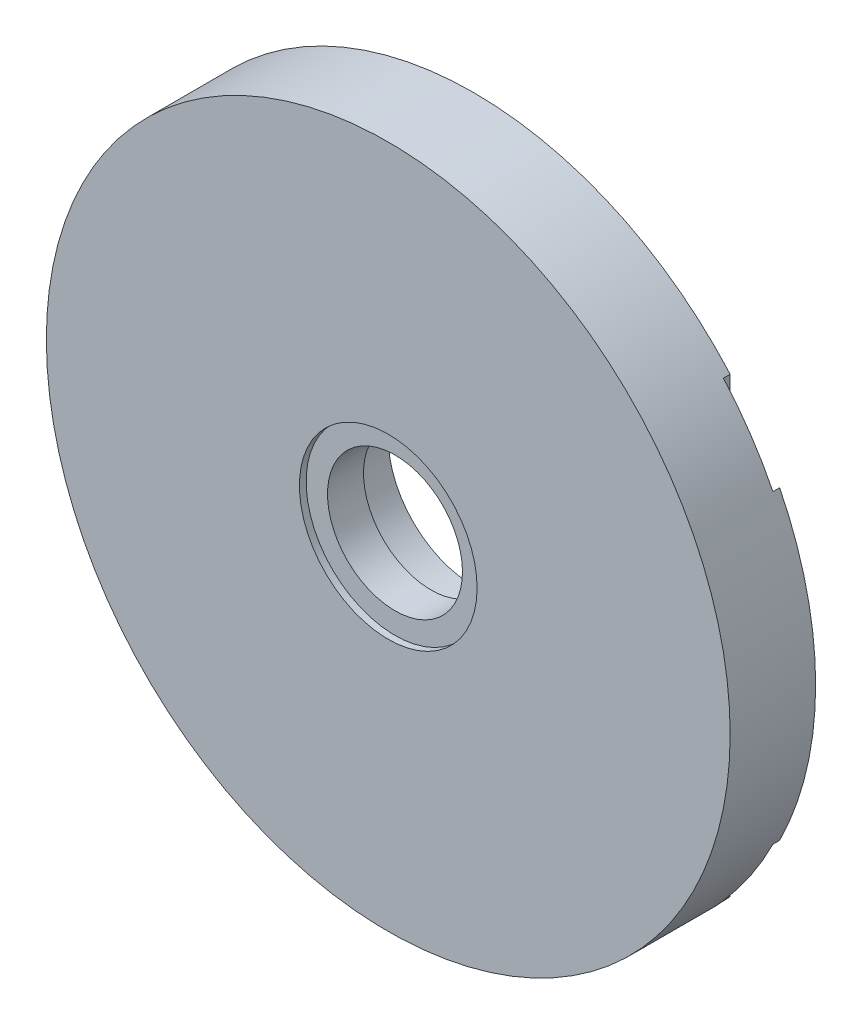
SolidWorks part; units mm, degrees
material "Plain Carbon Steel"
ref_plane "Front Plane" through (0, 0, 0) normal (1, 0, 0) x (0, 1, 0)
ref_plane "Top Plane" through (0, 0, 0) normal (0, 0, 1) x (0, 1, 0)
ref_plane "Right Plane" through (0, 0, 0) normal (0, 1, 0) x (-1, 0, 0)
sketch "Sketch1" plane through (0, 0, 0) normal (0, 0, 1) x (0, 1, 0)
  circle A0 centre (0, 0) radius 50.8
  circle A3 centre (0, 0) radius 10.025
  circle A4 centre (0, 0) radius 13.2
  circle A5 centre (0, 0) radius 12.7
  dimension "D1" = 101.6
  dimension "D2" = 20.05
  dimension "D3" = 26.4
  dimension "D4" = 25.4
extrude "Boss-Extrude1" add sketch "Sketch1" along normal blind 12.7 contours A0 A4 | A4 A3 | A5 A3 region at (0, -49.3632, 0) region at (0, -12.8266, 0) region at (0, -12.3408, 0)
extrude "Cut-Extrude1" cut sketch "Sketch1<3>" against normal blind 1 from surface contours A5 A3 | A4 A5 region at (0, -12.8266, 0) region at (0, -12.3408, 0) starting at face at (50.8, 0, 12.7)
sketch "Sketch1<3>" plane through (0, 0, 0) normal (0, 0, 1) x (0, 1, 0) same geometry as "Sketch1"
extrude "Cut-Extrude2" cut sketch "Sketch1<4>" along normal blind 6.35 contours A5 A3 region at (0, -12.3408, 0)
sketch "Sketch1<4>" plane through (0, 0, 0) normal (0, 0, 1) x (0, 1, 0) same geometry as "Sketch1"
sketch "Sketch2" plane through (0, 0, 0) normal (0, 0, -1) x (1, 0, 0)
  line L0 (0, 0) -> (-38.1, 0)
  line L1 (0, 0) -> (0, 12.7) construction
  line L2 (-38.1, 0) -> (-38.1, 38.1)
  line L3 (-38.1, 0) -> (-38.1, -38.1)
  line L4 (38.1, 0) -> (38.1, -38.1)
  line L5 (45.45, -38.1) -> (38.1, -38.1)
  line L6 (-38.1, 38.1) -> (-45.45, 38.1)
  line L7 (-45.45, 38.1) -> (-45.45, -38.1)
  line L8 (-45.45, -38.1) -> (-38.1, -38.1)
  line L9 (38.1, 0) -> (38.1, 38.1)
  line L10 (45.45, 38.1) -> (45.45, -38.1)
  line L11 (38.1, 38.1) -> (45.45, 38.1)
  circle M12 centre (0, 0) radius 50.8
  dimension "D1" = 38.1
  dimension "D2" = 38.1
  dimension "D5" = 38.1
  dimension "D7" = 7.35
extrude "Cut-Extrude3" cut sketch "Sketch2" against normal blind 1 contours L7 L3 L2 M12 | L10 L9 L4 M12 region at (-41.5444, 0, 0) region at (41.5444, 0, 0)
